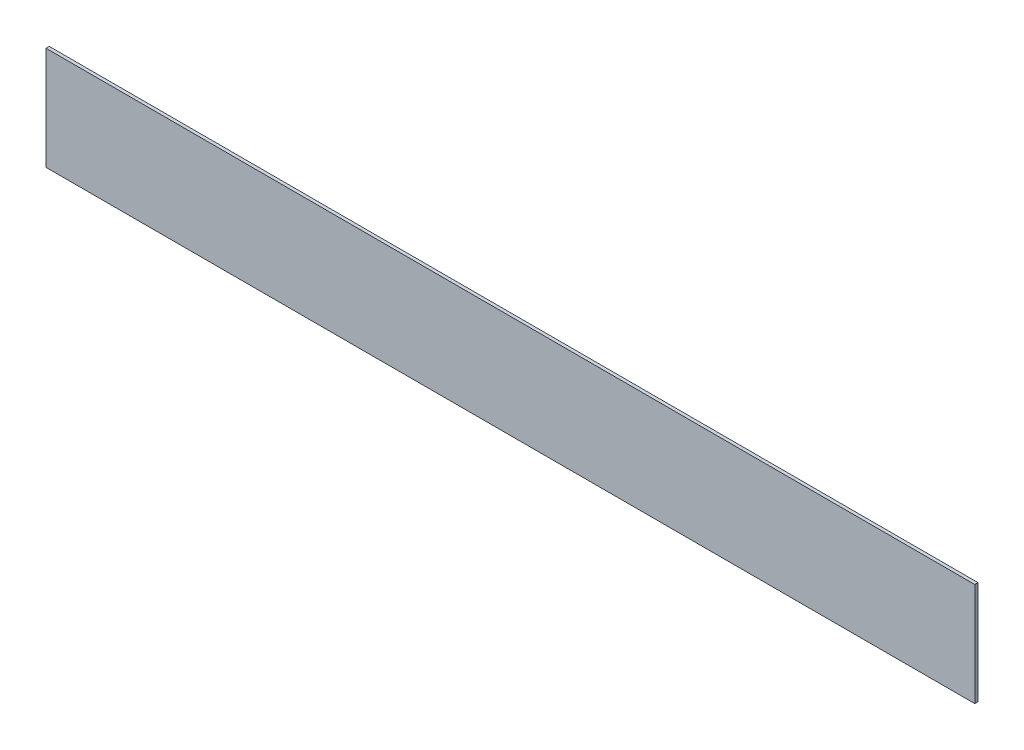
SolidWorks part; units mm, degrees
ref_plane "Front Plane" through (0, 0, 0) normal (0, 0, 1) x (1, 0, 0)
ref_plane "Top Plane" through (0, 0, 0) normal (0, 1, 0) x (1, 0, 0)
ref_plane "Right Plane" through (0, 0, 0) normal (1, 0, 0) x (0, 0, -1)
sketch "Sketch1" plane through (0, 0, 0) normal (0, 0, 1) x (1, 0, 0)
  line L1 (0, 0) -> (457.2, 0)
  line L2 (0, 0) -> (0, 50.8)
  line L3 (0, 50.8) -> (457.2, 50.8)
  line L4 (457.2, 0) -> (457.2, 50.8)
  dimension "D1" = 50.8
  dimension "D2" = 457.2
extrude "Boss-Extrude1" add sketch "Sketch1" along normal blind 1.5875
